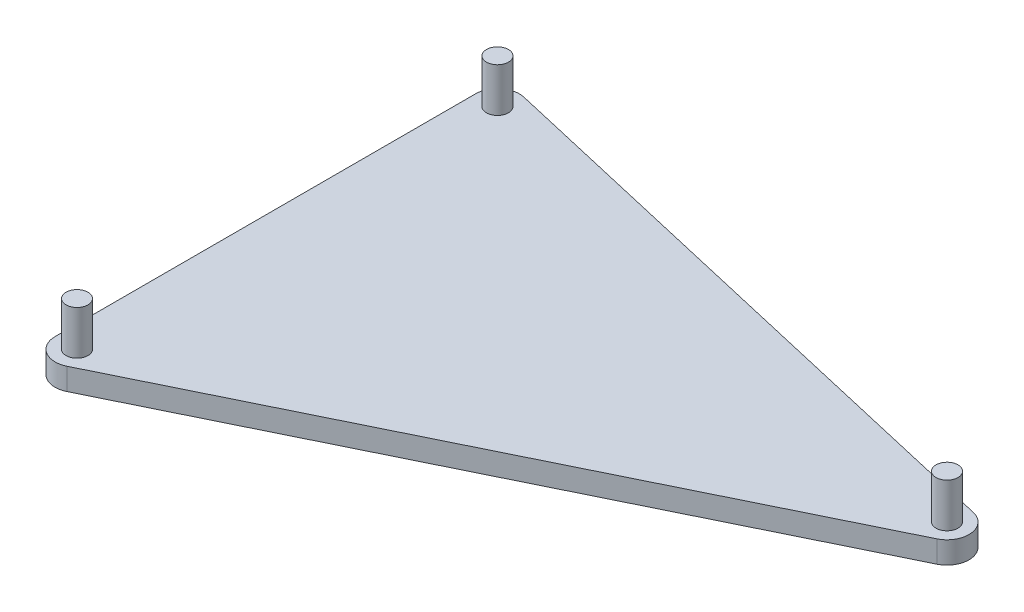
SolidWorks part; units mm, degrees
ref_plane "Front Plane" through (0, 0, 0) normal (0, 0, 1) x (1, 0, 0)
ref_plane "Top Plane" through (0, 0, 0) normal (0, 1, 0) x (1, 0, 0)
ref_plane "Right Plane" through (0, 0, 0) normal (1, 0, 0) x (0, 0, -1)
sketch "Sketch1" plane through (0, 0, 0) normal (0, 1, 0) x (1, 0, 0)
  line L0 (0, 0) -> (-266.16, 0) construction
  line L2 (-276.16, -130) -> (-276.16, 61.45) construction
  line L3 (-266.16, 61.45) -> (0, 0) construction
  line L4 (-266.16, -130) -> (0, 0) construction
  line L5 (-2.2496, -9.7437) -> (-268.4096, 51.7063) construction
  line L6 (-2.2496, -9.7437) -> (2.2496, 9.7437) construction
  line L7 (-268.4096, 51.7063) -> (-263.9104, 71.1937) construction
  line L8 (2.2496, 9.7437) -> (-263.9104, 71.1937) construction
  line L9 (-2.2496, -9.7437) -> (-263.9104, 71.1937) construction
  line L10 (-268.4096, 51.7063) -> (2.2496, 9.7437) construction
  line L11 (4.3888, -8.9855) -> (-261.7712, -138.9855) construction
  line L12 (4.3888, -8.9855) -> (-4.3888, 8.9855) construction
  line L13 (-261.7712, -138.9855) -> (-270.5488, -121.0145) construction
  line L14 (-4.3888, 8.9855) -> (-270.5488, -121.0145) construction
  line L15 (4.3888, -8.9855) -> (-270.5488, -121.0145) construction
  line L16 (-261.7712, -138.9855) -> (-4.3888, 8.9855) construction
  line L17 (-266.16, 61.45) -> (-266.16, -130) construction
  line L18 (-266.16, 61.45) -> (-266.16, -130) construction
  line L19 (-276.16, -130) -> (-256.16, -130) construction
  line L20 (-276.16, 61.45) -> (-256.16, 61.45) construction
  line L21 (-256.16, -130) -> (-256.16, 61.45) construction
  line L22 (-276.16, -130) -> (-256.16, 61.45) construction
  line L23 (-276.16, 61.45) -> (-256.16, -130) construction
  line L24 (-276.16, -130) -> (-276.16, 61.45)
  line L25 (-263.9104, 71.1937) -> (2.2496, 9.7437)
  line L26 (4.3888, -8.9855) -> (-261.7712, -138.9855)
  arc A0 (-276.16, 61.45) -> (-263.9104, 71.1937) centre (-266.16, 61.45) cw
  arc A1 (2.2496, 9.7437) -> (4.3888, -8.9855) centre (0, 0) cw
  arc A2 (-261.7712, -138.9855) -> (-276.16, -130) centre (-266.16, -130) cw
  circle A6 centre (-266.16, 61.45) radius 5
  circle A7 centre (0, 0) radius 5
  circle A8 centre (-266.16, -130) radius 5
  point P6 (-133.08, 30.725)
  point P7 (-133.08, -65)
  point P8 (-266.16, -34.275)
  dimension "D7" = 10
  dimension "D8" = 10
  dimension "D9" = 10
  dimension "D1" = 266.16
  dimension "D2" = 61.45
  dimension "D3" = 130
  dimension "D4" = 20
  dimension "D5" = 20
  dimension "D6" = 20
extrude "Boss-Extrude1" add sketch "Sketch1" along normal mid plane 10
sketch "Sketch3" plane through (0, 0, 0) normal (0, 1, 0) x (1, 0, 0)
  circle A0 centre (-266.16, 61.45) radius 5
  circle A1 centre (0, 0) radius 5
  circle A2 centre (-266.16, -130) radius 5
  dimension "D1" = 10
  dimension "D2" = 10
  dimension "D3" = 10
extrude "Boss-Extrude2" add sketch "Sketch3" along normal blind 25 and the other way blind 5
